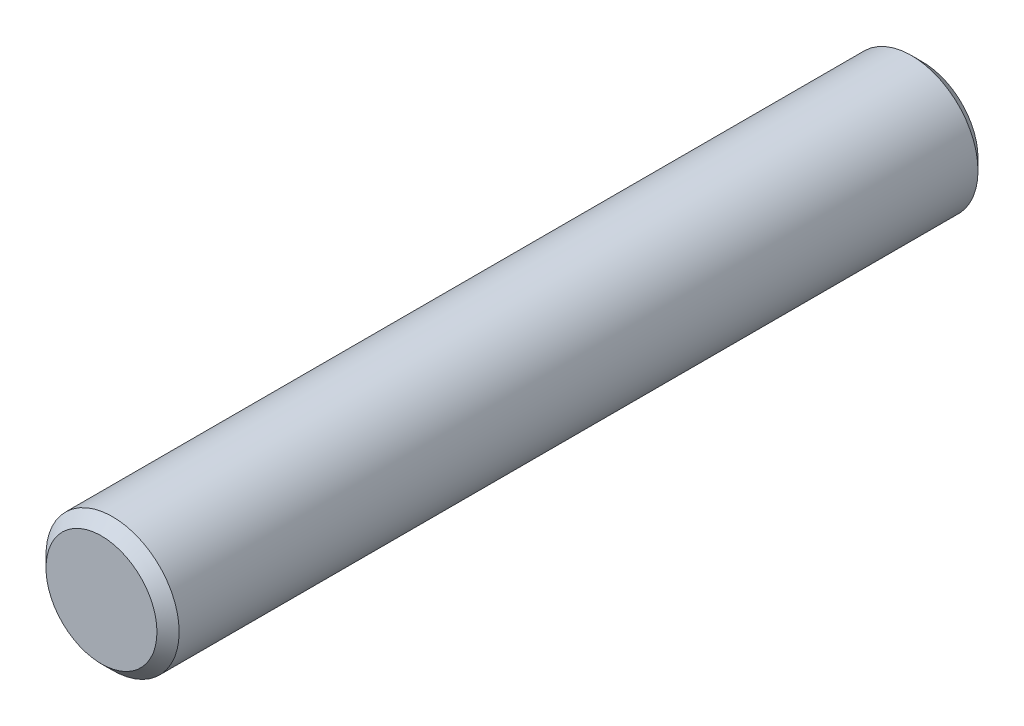
SolidWorks part; units mm, degrees
ref_plane "Front Plane" through (0, 0, 0) normal (0, 0, 1) x (1, 0, 0)
ref_plane "Top Plane" through (0, 0, 0) normal (0, 1, 0) x (1, 0, 0)
ref_plane "Right Plane" through (0, 0, 0) normal (1, 0, 0) x (0, 0, -1)
sketch "Sketch1" plane through (0, 0, 0) normal (0, 0, 1) x (1, 0, 0)
  circle A0 centre (0, 0) radius 3
  dimension "D1" = 6
extrude "Boss-Extrude1" add sketch "Sketch1" along normal blind 37
chamfer "Chamfer1" distance 0.5 angle 45 2 edges at (3, 0, 0) (3, 0, 37)
